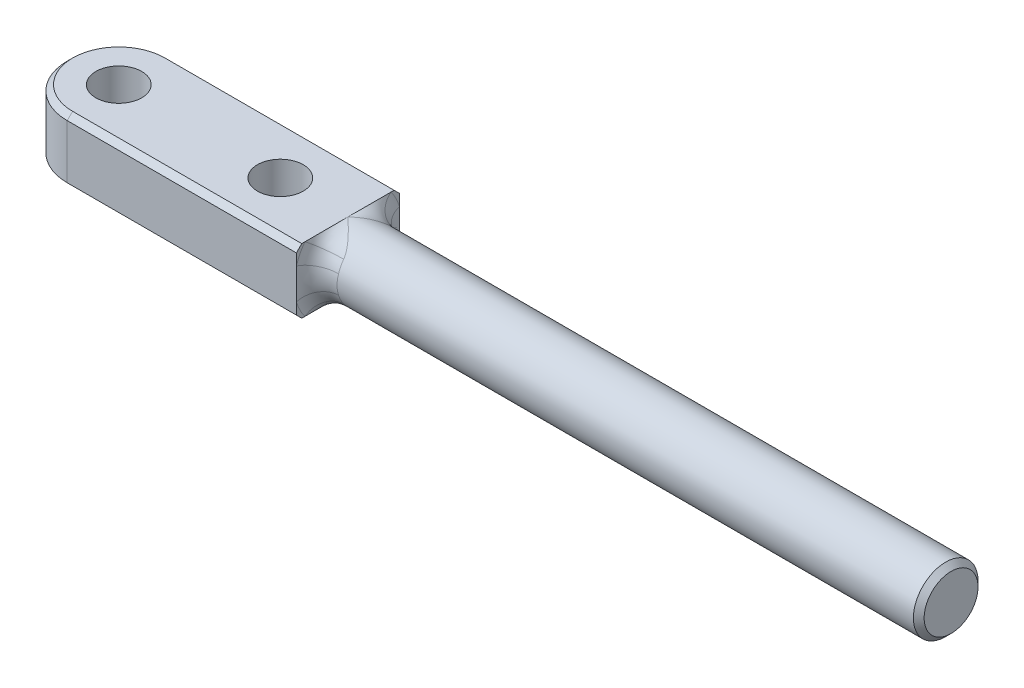
SolidWorks part; units mm, degrees
ref_plane "Front Plane" through (0, 0, 0) normal (0, 0, 1) x (1, 0, 0)
ref_plane "Top Plane" through (0, 0, 0) normal (0, 1, 0) x (1, 0, 0)
ref_plane "Right Plane" through (0, 0, 0) normal (1, 0, 0) x (0, 0, -1)
sketch "Sketch1" plane through (0, 0, 0) normal (0, 1, 0) x (1, 0, 0)
  line L1 (-91.0011, -14.1104) -> (-69.7238, -14.1104)
  line L3 (-91.0011, -23.6852) -> (-69.7238, -23.6852)
  line L4 (-69.7238, -14.1104) -> (-69.7238, -23.6852)
  arc A0 (-91.0011, -14.1104) -> (-91.0011, -23.6852) centre (-91.0011, -18.8978) ccw
  circle A1 centre (-91.0011, -18.8978) radius 2.1277
  circle A2 centre (-76.0011, -18.8978) radius 2.1277
  dimension "D1" = 15
extrude "Boss-Extrude1" add sketch "Sketch1" along normal blind 6
chamfer "Chamfer1" distance 0.5 angle 45 6 edges at (-80.3624, 0, 14.1104) (-95.7885, 0, 18.8978) (-80.3624, 0, 23.6852) (-80.3624, 6, 14.1104) (-95.7885, 6, 18.8978) (-80.3624, 6, 23.6852)
sketch "Sketch2" plane through (-69.7238, 0, 0) normal (1, 0, 0) x (0, 0, -1)
  circle A1 centre (-18.8978, 3) radius 3
extrude "Boss-Extrude2" add sketch "Sketch2" along normal blind 56
fillet "Fillet1" radius 2 2 edges at (-69.7238, 3, 15.8978) (-69.7238, 3, 21.8978)
chamfer "Chamfer2" distance 0.5 angle 45 1 edges at (-13.7238, 3, 15.8978)
